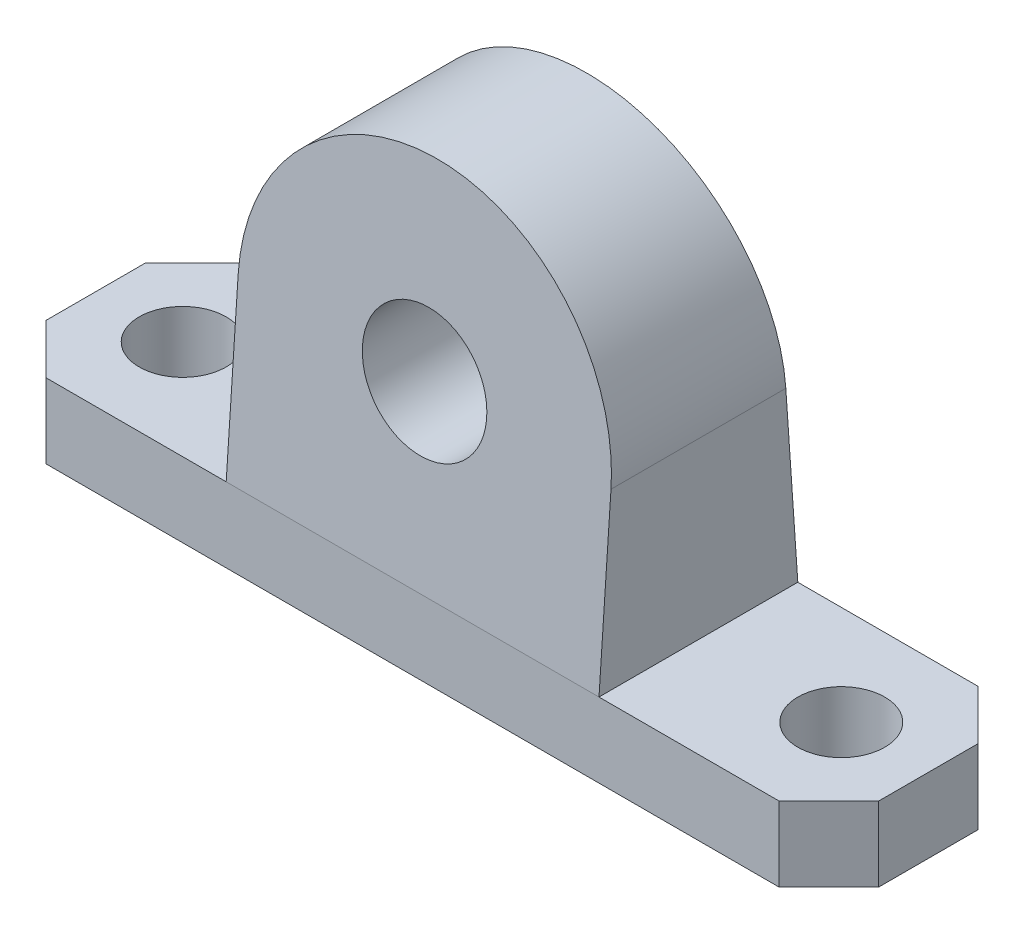
SolidWorks part; units mm, degrees
ref_plane "Front Plane" through (0, 0, 0) normal (0, 0, 1) x (1, 0, 0)
ref_plane "Top Plane" through (0, 0, 0) normal (0, 1, 0) x (1, 0, 0)
ref_plane "Right Plane" through (0, 0, 0) normal (1, 0, 0) x (0, 0, -1)
sketch "Sketch2" plane through (0, 0, 0) normal (0, 1, 0) x (1, 0, 0)
  line L0 (-29.5, 8) -> (-33.5, 4)
  line L1 (-29.5, -8) -> (29.5, -8)
  line L2 (-33.5, -4) -> (-33.5, 4)
  line L3 (-29.5, 8) -> (29.5, 8)
  line L4 (33.5, -4) -> (33.5, 4)
  line L5 (-33.5, -8) -> (33.5, 8) construction
  line L6 (-33.5, 8) -> (33.5, -8) construction
  line L7 (29.5, 8) -> (33.5, 4)
  line L8 (33.5, -4) -> (29.5, -8)
  line L9 (-33.5, -4) -> (-29.5, -8)
  point P0 (0, 0)
  dimension "D1" = 16
  dimension "D2" = 67
  dimension "D3" = 4
  dimension "D4" = 4
  dimension "D5" = 4
  dimension "D6" = 4
  dimension "D7" = 4
  dimension "D8" = 4
  dimension "D9" = 4
  dimension "D10" = 4
extrude "Boss-Extrude2" add sketch "Sketch2" along normal blind 6
sketch "Sketch3" plane through (0, 6, 0) normal (0, 1, 0) x (1, 0, 0)
  line L0 (29.5, 8) -> (-29.5, 8) construction
  line L1 (-15, -8) -> (15, -8)
  line L2 (-15, -8) -> (-15, 8)
  line L3 (-15, 8) -> (15, 8)
  line L4 (15, -8) -> (15, 8)
  line L5 (-15, -8) -> (15, 8) construction
  line L6 (-15, 8) -> (15, -8) construction
  point P0 (0, 0)
  dimension "D1" = 30
extrude "Boss-Extrude3" add sketch "Sketch3" along normal blind 29
sketch "Sketch4" plane through (0, 0, 8) normal (0, 0, 1) x (1, 0, 0)
  line L0 (-15, 35) -> (15, 35) construction
  line L1 (15, 35) -> (15, 6) construction
  line L2 (-15, 35) -> (-15, 6) construction
  line L3 (15, 35) -> (15, 20)
  line L4 (-15, 35) -> (15, 35)
  line L5 (-15, 35) -> (-15, 20)
  arc A0 (15, 20) -> (-15, 20) centre (0, 20) ccw
  line M4 (15, 6) -> (15, 35)
  line M5 (15, 35) -> (-15, 35)
  line M6 (-15, 35) -> (-15, 6)
  dimension "D1" = 30
extrude "Cut-Extrude1" cut sketch "Sketch4" against normal up to surface (16 mm away) contours A0 L4 M6 | A0 M4 M5 region at (-11.6495, 31.6495, 8) region at (11.6495, 31.6495, 8) up to face at (0, 11.75, -8)
sketch "Sketch5" plane through (-15, 0, 0) normal (-1, 0, 0) x (0, 0, 1)
  line L1 (8, 35) -> (-8, 35) construction
  line L2 (8, 20) -> (8, 35) construction
  line L3 (-6, 35) -> (-8, 6)
  line L4 (-6, 35) -> (-8, 35)
  line L5 (8, 6) -> (6, 35)
  line L6 (-8, 35) -> (-8, 20) construction
  line L7 (-8, 35) -> (-8, 6)
  line L8 (6, 35) -> (8, 35)
  line L9 (8, 35) -> (8, 6)
  dimension "D1" = 12
  dimension "D2" = 2
extrude "Cut-Extrude2" cut sketch "Sketch5" against normal blind 30
sketch "Sketch6" plane through (0, 0, 0) normal (0, -1, 0) x (1, 0, 0)
  line L0 (33.5, 4) -> (33.5, -4) construction
  circle A0 centre (-26.5, 0) radius 3.5
  circle A1 centre (26.5, 0) radius 3.5
  dimension "D1" = 7
  dimension "D2" = 7
  dimension "D3" = 53
  dimension "D4" = 7
extrude "Cut-Extrude3" cut sketch "Sketch6" against normal blind 6
sketch "Sketch7" plane through (0, 0, -8) normal (0, 0, -1) x (-1, 0, 0)
  circle A0 centre (0, 20) radius 5
  point P3 (0, 0)
  dimension "D1" = 10
extrude "Cut-Extrude4" cut sketch "Sketch7" against normal up to surface (15.0345 mm away) up to face at (0, 16.75, 7.2586)
sketch "Sketch8" plane through (0, 0, -8) normal (0, 0, -1) x (-1, 0, 0)
  circle A0 centre (0, 20) radius 7
  circle A1 centre (0, 20) radius 5 construction
  circle A2 centre (0, 20) radius 5
  dimension "D1" = 14
extrude "Boss-Extrude4" add sketch "Sketch8" against normal up to surface and the other way blind 1 up to face at (0, 15, -7.3793)
